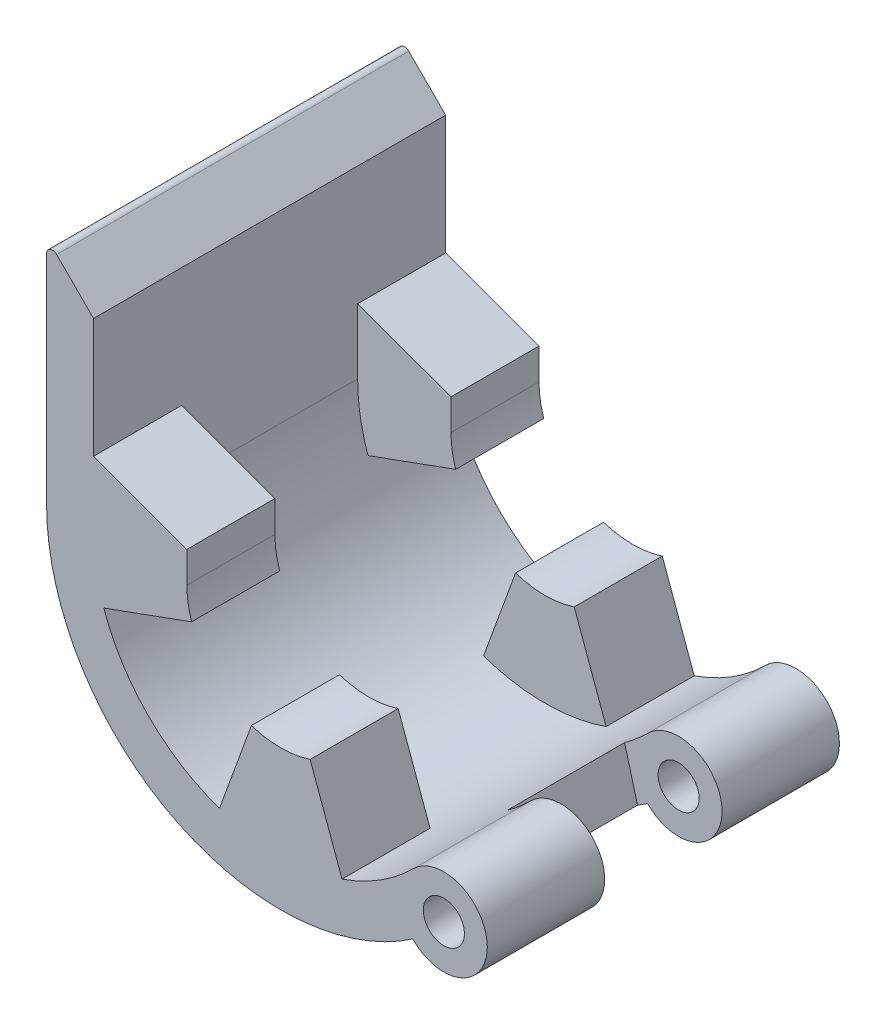
SolidWorks part; units mm, degrees
ref_plane "Спереди" through (0, 0, 0) normal (0, 0, 1) x (1, 0, 0)
ref_plane "Сверху" through (0, 0, 0) normal (0, 1, 0) x (1, 0, 0)
ref_plane "Справа" through (0, 0, 0) normal (1, 0, 0) x (0, 0, -1)
sketch "Эскиз1" plane through (0, 0, 0) normal (0, 0, 1) x (1, 0, 0)
  line L5 (0, -1010.5) -> (0, 48989.5) construction
  line L7 (-8, 0) -> (-8, 2.6458)
  line L8 (9.2894, -12.9657) -> (10.3944, -17.0282)
  line L9 (3.3591, -3.3591) -> (35358.6982, -35358.6982) construction
  line L24 (-15.95, 15.7071) -> (-15.95, 0)
  line L25 (-1000, 0) -> (49000, 0) construction
  line L30 (-15.95, 15.7071) -> (-19.0964, 18.8536)
  line L31 (-19.95, 18.5) -> (-19.95, 0)
  line L35 (-2.5, -7.5993) -> (-5.2197, -15.0717)
  line L36 (5.2197, -15.0717) -> (2.5, -7.5993)
  line L37 (-8, 2.6458) -> (-15.95, 5.5394)
  line L38 (-7.5993, -2.5) -> (-15.0717, -5.2197)
  circle A3 centre (13.8946, -13.8946) radius 4.2 construction
  arc A15 (11.246, -16.4782) -> (11.2784, -11.2784) centre (13.8946, -13.8946) ccw
  circle A16 centre (13.8946, -13.8946) radius 1.75
  arc A18 (-19.0964, 18.8536) -> (-19.95, 18.5) centre (-19.45, 18.5) ccw
  arc A24 (-19.95, 0) -> (11.246, -16.4782) centre (0, 0) ccw
  arc A25 (-15.95, 0) -> (11.2784, -11.2784) centre (0, 0) ccw
  arc A29 (-2.5, -7.5993) -> (2.5, -7.5993) centre (0, 0) ccw
  arc A30 (-8, 0) -> (-7.5993, -2.5) centre (0, 0) ccw
  point P4 (9.8419, -14.997)
  dimension "D7" = 40
  dimension "D8" = 8.4
  dimension "D9" = 40
  dimension "D10" = 5
  dimension "D11" = 45
  dimension "D12" = 7.4
  dimension "D13" = 3.5
  dimension "D15" = 0.5
  dimension "D16" = 4
  dimension "D19" = 45
  dimension "D3" = 8
  dimension "D4" = 15.95
  dimension "D5" = 19.95
  dimension "D2" = 5.1458
  dimension "D6" = 18.5
extrude "Бобышка-Вытянуть1" add sketch "Эскиз1" along normal mid plane 30 contours A25 L24 L30 A18 L31 A24 A15 | A15 A16 region at (-16.4437, 2.7697, 0) region at (10.3904, -12.2476, 0)
extrude "Бобышка-Вытянуть2" add sketch "Эскиз1<3>" against normal blind 7.5 from surface contours A30 L37 L24 A25 L38 | A29 L35 A25 L36 | A25 A15 region at (-12.3337, 0.0937, 0) region at (0, -12.2195, 0) starting at face at (-10.1274, 1.0074, 15)
sketch "Эскиз1<3>" plane through (0, 0, 0) normal (0, 0, 1) x (1, 0, 0) same geometry as "Эскиз1"
extrude "Бобышка-Вытянуть3" add sketch "Эскиз1<4>" along normal blind 7.5 from surface contours A30 L37 L24 A25 L38 | A29 L35 A25 L36 | A25 A15 region at (-12.3337, 0.0937, 0) region at (0, -12.2195, 0) starting at face at (-10.1274, 1.0074, -15)
sketch "Эскиз1<4>" plane through (0, 0, 0) normal (0, 0, 1) x (1, 0, 0) same geometry as "Эскиз1"
extrude "Вырез-Вытянуть2" cut sketch "Эскиз1<5>" against normal mid plane 10 contours A15 A16 region at (10.3904, -12.2476, 0)
sketch "Эскиз1<5>" plane through (0, 0, 0) normal (0, 0, 1) x (1, 0, 0) same geometry as "Эскиз1"
sketch "Эскиз2" plane through (0, 0, 0) normal (0, 0, 1) x (1, 0, 0)
  line L0 (-11.25, 0) -> (11.25, 0)
  arc A0 (-11.25, 0) -> (11.25, 0) centre (0, 0) cw
  dimension "D1" = 11.25
revolve "Вырез-Повернуть1" [suppressed] cut sketch "Эскиз2" angle 360 about L0
